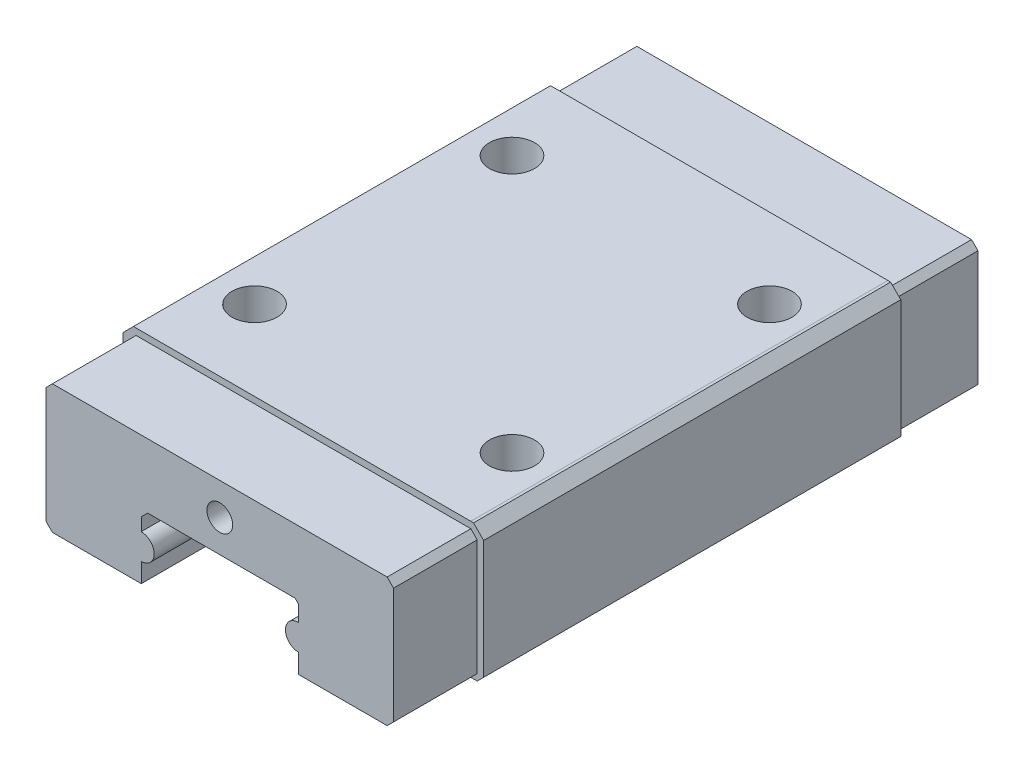
SolidWorks part; units mm, degrees
ref_plane "Front Plane" through (0, 0, 0) normal (0, 0, 1) x (1, 0, 0)
ref_plane "Top Plane" through (0, 0, 0) normal (0, 1, 0) x (1, 0, 0)
ref_plane "Right Plane" through (0, 0, 0) normal (1, 0, 0) x (0, 0, -1)
sketch "Sketch1" plane through (0, 0, 0) normal (0, 0, 1) x (1, 0, 0)
  line L0 (-13.5, -5) -> (-6.1, -5)
  line L1 (-13, 5) -> (13, 5)
  line L2 (-13.5, 4.5) -> (-13.5, -4.5)
  line L3 (-13, -5) -> (13, -5)
  line L4 (13.5, 4.5) -> (13.5, -4.5)
  line L5 (-13.5, 5) -> (13.5, -5) construction
  line L6 (-13.5, -5) -> (13.5, 5) construction
  line L7 (-6.1, -5) -> (-6.1, -3.5)
  line L8 (-5.6, 0) -> (5.85, 0)
  line L9 (6.1, -0.25) -> (6.1, -1.5)
  line L10 (6.1, -5) -> (13.5, -5)
  line L11 (-13.5, 4.5) -> (-13, 5)
  line L12 (-6.1, -1.5) -> (-6.1, -0.5)
  line L13 (6.1, -3.5) -> (6.1, -5)
  line L14 (-13.5, -4.5) -> (-13, -5)
  line L15 (13, 5) -> (13.5, 4.5)
  line L16 (13, -5) -> (13.5, -4.5)
  line L17 (5.85, 0) -> (6.1, -0.25)
  line L18 (-6.1, -0.5) -> (-5.6, 0)
  arc A0 (-6.1, -1.5) -> (-6.1, -3.5) centre (-6.1, -2.5) cw
  arc A1 (6.1, -1.5) -> (6.1, -3.5) centre (6.1, -2.5) ccw
  circle A2 centre (0, 2.5) radius 1
  point P0 (0, 0)
  point P8 (-6.1, 0)
  point P9 (6.1, 0)
  dimension "D6" = 2.5
  dimension "D7" = 2
  dimension "D16" = 1
  dimension "D17" = 1
  dimension "D1" = 27
  dimension "D2" = 10
  dimension "D3" = 7.4
  dimension "D4" = 7.4
  dimension "D5" = 5
  dimension "D14" = 2.5
  dimension "D15" = 2.5
extrude "Boss-Extrude1" add sketch "Sketch1" along normal blind 45.4 contours L9 A1 L13 L3 L16 L4 L15 L1 L11 L2 L14 L0 L7 A0 L12 L18 L8 L17 region at (-0.0027, 0.6555, 0)
sketch "Sketch5" plane through (0, 0, 45.4) normal (0, 0, 1) x (1, 0, 0)
  line L0 (13, 5.5) -> (13.2108, 5.4963)
  line L1 (13.3536, 5.3536) -> (13.2108, 5.4963)
  line L2 (-14, 4.5) -> (-14, 4.7071)
  line L3 (-13.8536, 4.8536) -> (-14, 4.7071)
  line L5 (-13.5, -5) -> (-6.1, -5)
  line L7 (13.5, -5) -> (6.1, -5)
  line L10 (-6.1, -5) -> (-6.1, -3.5)
  line L11 (-6.1, -5) -> (-6.1, -3.5)
  line L41 (-14, -4.5) -> (-13.5, -5)
  line L42 (14, -4.5) -> (13.5, -5)
  line L46 (6.1, -3.5) -> (6.1, -5)
  line L47 (-5.6, 0) -> (5.85, 0)
  line L48 (6.1, -0.25) -> (6.1, -1.5)
  line L49 (5.85, 0) -> (6.1, -0.25)
  line L50 (-6.1, -0.5) -> (-5.6, 0)
  line L51 (-6.1, -1.5) -> (-6.1, -0.5)
  line L52 (6.1, -3.5) -> (6.1, -5)
  line L53 (-5.6, 0) -> (5.85, 0)
  line L54 (6.1, -0.25) -> (6.1, -1.5)
  line L55 (5.85, 0) -> (6.1, -0.25)
  line L56 (-6.1, -0.5) -> (-5.6, 0)
  line L57 (-6.1, -1.5) -> (-6.1, -0.5)
  line L942 (-14, 4.5) -> (-14, -4.5)
  line L943 (-14, 4.5) -> (-14, -4.5)
  line L948 (-13.2071, 5.5) -> (13, 5.5)
  line L949 (-13.8536, 4.8536) -> (-13.2071, 5.5)
  line L950 (-13.2071, 5.5) -> (13, 5.5)
  line L951 (-13.8536, 4.8536) -> (-13.2071, 5.5)
  line L960 (14, 4.7071) -> (14, -4.5)
  line L961 (13.3536, 5.3536) -> (14, 4.7071)
  line L962 (14, 4.7071) -> (14, -4.5)
  line L963 (13.3536, 5.3536) -> (14, 4.7071)
  arc A13 (6.1, -1.5) -> (6.1, -3.5) centre (6.1, -2.5) ccw
  arc A14 (-6.1, -3.5) -> (-6.1, -1.5) centre (-6.1, -2.5) ccw
  arc A15 (6.1, -1.5) -> (6.1, -3.5) centre (6.1, -2.5) ccw
  arc A16 (-6.1, -3.5) -> (-6.1, -1.5) centre (-6.1, -2.5) ccw
  circle A17 centre (0, 2.5) radius 1
  circle A18 centre (0, 2.5) radius 1
  dimension "D1" = 0.5
  dimension "D2" = 0.5
  dimension "D3" = 0.5
  dimension "D4" = 0
  dimension "D5" = 0
  dimension "D6" = 0
extrude "Boss-Extrude2" add sketch "Sketch5" against normal blind 32.4 from offset 6.5 offset against normal yes
hole_wizard "M5x0.8 Tapped Hole1" positions "Sketch6" profile "Sketch7" tap size "M5x0.8" standard "ANSI Metric"
sketch "Sketch6" plane through (0, 5.5, 0) normal (0, 1, 0) x (1, 0, 0)
  line L1 (-20.8678, -22.7) -> (18.0804, -22.7) construction
  line L3 (0, 1.0246) -> (0, -48.1731) construction
  point P0 (-10, -12.7)
  point P2 (-10, -32.7)
  point P4 (10, -32.7)
  point P6 (10, -12.7)
  dimension "D1" = 10
  dimension "D2" = 10
  dimension "D3" = 10
  dimension "D4" = 10
sketch "Sketch7" plane through (-10, 5.5, 12.7) normal (1, 0, 0) x (0, 0, 1)
  line L0 (0, 0) -> (0, 5.0515)
  line L1 (0, 5.0515) -> (1.75, 4)
  line L2 (1.75, 4) -> (1.75, 0)
  line L5 (1.75, 0) -> (0, 0)
  line L10 (0, 5.0515) -> (-1.75, 4) construction
  line L11 (0, -6.35) -> (0, 107.95) construction
  dimension "Tap Drill Dia." = 3.5
  dimension "Tap Drill Depth" = 4
  dimension "Drill Angle" = 118
equation "\"32.4.00mm\"=10"
